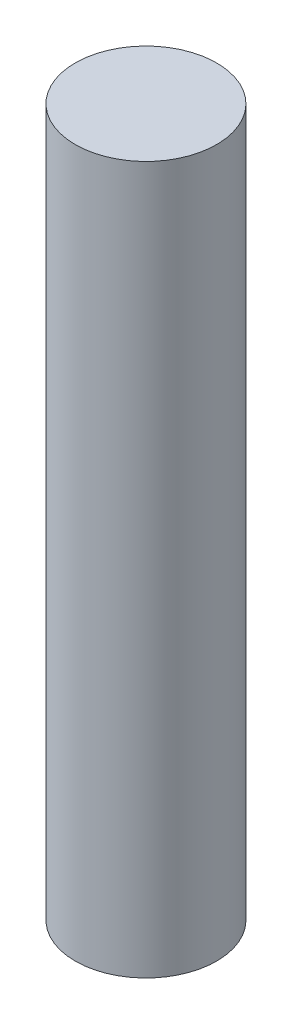
SolidWorks part; units mm, degrees
ref_plane "前视基准面" through (0, 0, 0) normal (0, 0, 1) x (1, 0, 0)
ref_plane "上视基准面" through (0, 0, 0) normal (0, 1, 0) x (1, 0, 0)
ref_plane "右视基准面" through (0, 0, 0) normal (1, 0, 0) x (0, 0, -1)
sketch "草图1" plane through (0, 0, 0) normal (0, 1, 0) x (1, 0, 0)
  circle A0 centre (0, 0) radius 5
  dimension "D1" = 10
extrude "凸台-拉伸1" add sketch "草图1" along normal blind 50
hole_wizard "M4 螺纹孔1" positions "草图4" profile "草图5" tap size "M4" standard "GB"
sketch "草图4" plane through (0, 0, 0) normal (0, -1, 0) x (-1, 0, 0)
  point P0 (0, 0)
sketch "草图5" plane through (0, 0, 0) normal (1, 0, 0) x (0, 0, -1)
  line L0 (0, 0) -> (0, 15.9914)
  line L1 (0, 15.9914) -> (1.65, 15)
  line L2 (1.65, 15) -> (1.65, 0)
  line L5 (1.65, 0) -> (0, 0)
  line L10 (0, 15.9914) -> (-1.65, 15) construction
  line L11 (0, -6.35) -> (0, 107.95) construction
  dimension "螺纹孔钻头直径" = 3.3
  dimension "螺纹孔钻头深度" = 15
  dimension "导头角度" = 118
cosmetic thread "孔螺蚊线1" parameters "D1"=8, "D2"=4
